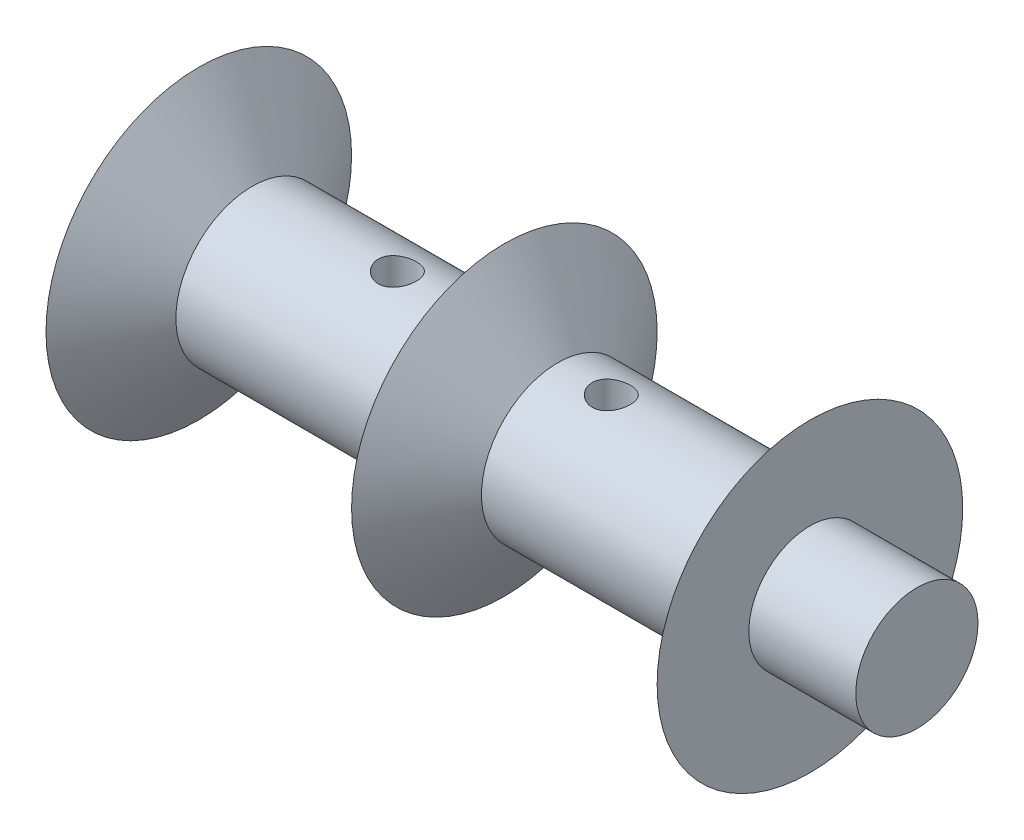
SolidWorks part; units mm, degrees
ref_plane "Front Plane" through (0, 0, 0) normal (0, 0, 1) x (1, 0, 0)
ref_plane "Top Plane" through (0, 0, 0) normal (0, 1, 0) x (1, 0, 0)
ref_plane "Right Plane" through (0, 0, 0) normal (1, 0, 0) x (0, 0, -1)
sketch "Sketch1" plane through (0, 0, 0) normal (0, 0, 1) x (1, 0, 0)
  line L0 (20, 0) -> (-20, 0)
  line L1 (-20, 10) -> (-20, 0)
  line L2 (16.5, 5) -> (20, 10)
  line L3 (-20, 10) -> (-16.5, 5)
  line L4 (-16.5, 5) -> (-3.5, 5)
  line L5 (-3.5, 5) -> (0, 10)
  line L6 (0, 0) -> (0, 1.6747) construction
  line L7 (20, 10) -> (20, 0)
  line L10 (16.5, 5) -> (3.5, 5)
  line L11 (3.5, 5) -> (0, 10)
  point P3 (0, 0)
  dimension "D1" = 40
  dimension "D2" = 5
  dimension "D3" = 3.5
  dimension "D4" = 3.5
  dimension "D5" = 13
  dimension "D6" = 10
  dimension "D7" = 5
revolve "Revolve1" add sketch "Sketch1" angle 360 about L0
sketch "Sketch2" plane through (-20, 0, 0) normal (-1, 0, 0) x (0, 0, 1)
  line L0 (-1.5, 2) -> (-1.5, -2)
  line L1 (0, 0) -> (0, -0.3908) construction
  line L2 (1.5, 2) -> (1.5, -2)
  circle A0 centre (0, 0) radius 2.5
  dimension "D1" = 5
  dimension "D2" = 3
extrude "Cut-Extrude1" cut sketch "Sketch2" against normal blind 9 contours L2 A0 L0 region at (-20, 0, 0)
sketch "Sketch3" plane through (-20, 0, 0) normal (-1, 0, 0) x (0, 0, 1)
  circle A0 centre (0, 0) radius 2.5
extrude "Cut-Extrude2" cut sketch "Sketch3" against normal blind 2.5
sketch "Sketch4" plane through (20, 0, 0) normal (1, 0, 0) x (0, 0, -1)
  circle A0 centre (0, 0) radius 4
extrude "Boss-Extrude1" add sketch "Sketch4" along normal blind 7
sketch "Sketch5" plane through (0, 0, 0) normal (0, 1, 0) x (1, 0, 0)
  line L0 (0, 0) -> (0, 6.0101) construction
  circle A0 centre (-7, 0) radius 1.25
  circle A1 centre (7, 0) radius 1.25
  dimension "D1" = 7
  dimension "D2" = 2.5
extrude "Cut-Extrude3" cut sketch "Sketch5" against normal through all and the other way through all
